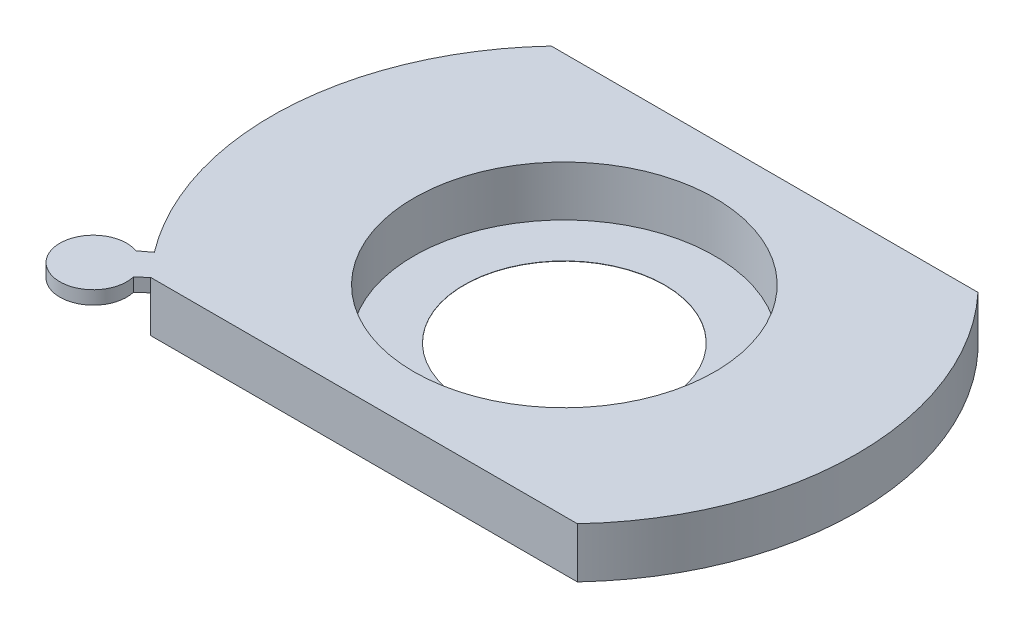
SolidWorks part; units mm, degrees
material "1345 Alloy"
ref_plane "Front Plane" through (0, 0, 0) normal (0, 0, 1) x (1, 0, 0)
ref_plane "Top Plane" through (0, 0, 0) normal (0, 1, 0) x (1, 0, 0)
ref_plane "Right Plane" through (0, 0, 0) normal (1, 0, 0) x (0, 0, -1)
sketch "Sketch1" plane through (0, 0, 0) normal (0, 1, 0) x (1, 0, 0)
  line L0 (-1712.4333, 578.2677) -> (-1658.0172, 559.892) construction
  line L1 (-1682.6566, 611.2885) -> (-1644.8226, 597.5438) construction
  line L2 (-1769.951, 660.0706) -> (-1712.4333, 741.8735) construction
  circle A0 centre (0, 0) radius 1750
  arc A3 (-1712.4333, 578.2677) -> (-1712.4333, 741.8735) centre (-1769.951, 660.0706) cw construction
  arc A4 (-1712.4333, 741.8735) -> (-1682.6566, 611.2885) centre (-1769.951, 660.0706) cw construction
extrude "Boss-Extrude1" add sketch "Sketch1" along normal blind 500
sketch "Sketch2" plane through (0, 500, 0) normal (0, 1, 0) x (1, 0, 0)
  circle A0 centre (0, 0) radius 900
extrude "Cut-Extrude2" cut sketch "Sketch2" against normal blind 300
sketch "Sketch9" plane through (0, 0, 0) normal (0, -1, 0) x (1, 0, 0)
  line L1 (-2106.3119, -1198.0599) -> (2106.3119, -1198.0599)
  line L2 (-2106.3119, -1198.0599) -> (-2106.3119, 1198.0599)
  line L3 (-2106.3119, 1198.0599) -> (2106.3119, 1198.0599)
  line L4 (2106.3119, -1198.0599) -> (2106.3119, 1198.0599)
  line L5 (-2106.3119, -1198.0599) -> (2106.3119, 1198.0599) construction
  line L6 (-2106.3119, 1198.0599) -> (2106.3119, -1198.0599) construction
  line L7 (-2636.6179, -2082.9122) -> (2636.6179, -2082.9122)
  line L8 (-2636.6179, -2082.9122) -> (-2636.6179, 2082.9122)
  line L9 (-2636.6179, 2082.9122) -> (2636.6179, 2082.9122)
  line L10 (2636.6179, -2082.9122) -> (2636.6179, 2082.9122)
  line L11 (-2636.6179, -2082.9122) -> (2636.6179, 2082.9122) construction
  line L12 (-2636.6179, 2082.9122) -> (2636.6179, -2082.9122) construction
  point P0 (0, 0)
  point P6 (0, 0)
extrude "Cut-Extrude10" cut sketch "Sketch9" against normal through all both and the other way through all
sketch "Sketch3" plane through (0, 0, 0) normal (0, -1, 0) x (1, 0, 0)
  circle A0 centre (0, 0) radius 600
extrude "Cut-Extrude3" cut sketch "Sketch3" against normal blind 300
shell "Shell1" thickness 1.5 removed face at (0, 0, -600)
sketch "Sketch10" plane through (0, 198.5, 0) normal (0, -1, 0) x (1, 0, 0)
  line L1 (2226.5426, -1551.0392) -> (-2226.5426, -1551.0392)
  line L2 (2226.5426, -1551.0392) -> (2226.5426, 1551.0392)
  line L3 (2226.5426, 1551.0392) -> (-2226.5426, 1551.0392)
  line L4 (-2226.5426, -1551.0392) -> (-2226.5426, 1551.0392)
  line L5 (2226.5426, -1551.0392) -> (-2226.5426, 1551.0392) construction
  line L6 (2226.5426, 1551.0392) -> (-2226.5426, -1551.0392) construction
  point P0 (0, 0)
extrude "Cut-Extrude11" cut sketch "Sketch10" along normal through all
sketch "Sketch12" plane through (0, 500, 0) normal (0, 1, 0) x (1, 0, 0)
  line L0 (-1275.7204, -1197.9305) -> (-1329.4274, -1248.3625)
  line L1 (-1275.7204, -1197.9305) -> (-1329.4274, -1248.3625)
  line L2 (-1456.8867, -1104.0663) -> (-1394.7434, -1056.9725)
  line L3 (-1212.6439, -1163.1539) -> (-1394.7434, -1056.9725) construction
  line L4 (-1329.4274, -1248.3625) -> (-1275.8583, -1198.0599) construction
  line L5 (1275.5989, -1198.0599) -> (-1275.5989, -1198.0599) construction
  arc A0 (-1275.5989, -1198.0599) -> (-1524.5473, -859.2179) centre (0, 0) cw
  arc A2 (-1329.4274, -1248.3625) -> (-1456.8867, -1104.0663) centre (-1524.5473, -1292.2737) cw
  arc A3 (-1275.7204, -1197.9305) -> (-1275.5989, -1198.0599) centre (0, 0) cw construction
  point P4 (-1566.0986, -1212.0375)
  point P5 (-1616.6545, -1140.7147)
  point P6 (0, 0)
  point P12 (-1546.5607, -965.2295)
  point P16 (-1524.5473, -1289.7823)
  point P19 (-1524.5473, -1292.2737)
  arc M6 (-1275.5989, 1198.0599) -> (-1275.5989, -1198.0599) centre (0, 0) ccw
extrude "Boss-Extrude2" add sketch "Sketch12" against normal blind 80 contours A2 L0 L2 M6 region at (-1511.5348, 500, 1280.7775)
